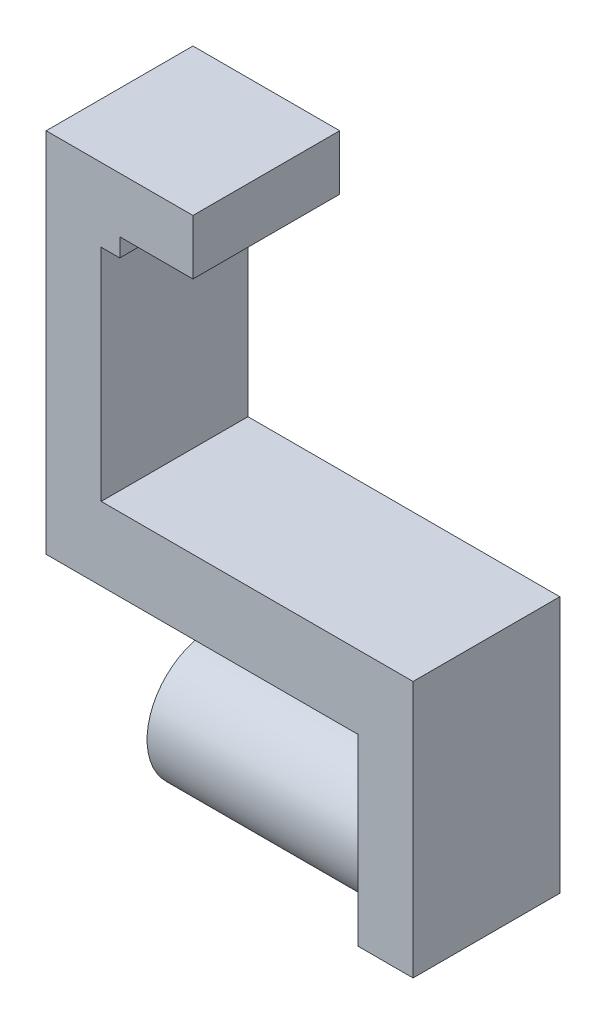
SolidWorks part; units mm, degrees
material "ASTM A36 Steel"
ref_plane "Front Plane" through (0, 0, 0) normal (0, 0, 1) x (1, 0, 0)
ref_plane "Top Plane" through (0, 0, 0) normal (0, 1, 0) x (1, 0, 0)
ref_plane "Right Plane" through (0, 0, 0) normal (1, 0, 0) x (0, 0, -1)
sketch "Sketch1" plane through (0, 0, 0) normal (1, 0, 0) x (0, 0, -1)
  circle A0 centre (0, 0) radius 11.1125
  dimension "D1" = 22.225
extrude "Boss-Extrude1" add sketch "Sketch1" against normal blind 38.1
sketch "Sketch2" plane through (0, 0, 0) normal (0, 0, 1) x (1, 0, 0)
  line L1 (0, -11.1125) -> (9.525, -11.1125)
  line L2 (0, -11.1125) -> (0, 20.6375)
  line L3 (0, 20.6375) -> (9.525, 20.6375)
  line L4 (9.525, -11.1125) -> (9.525, 20.6375)
  dimension "D1" = 9.525
  dimension "D2" = 31.75
  dimension "D3" = 11.1125
extrude "Boss-Extrude2" add sketch "Sketch2" along normal blind 12.7 and the other way blind 12.7
sketch "Sketch3" plane through (0, 0, 0) normal (0, 0, 1) x (1, 0, 0)
  line L1 (-53.975, 20.6375) -> (9.525, 20.6375)
  line L2 (-53.975, 20.6375) -> (-53.975, 33.3375)
  line L3 (-53.975, 33.3375) -> (9.525, 33.3375)
  line L4 (9.525, 20.6375) -> (9.525, 33.3375)
  dimension "D1" = 63.5
  dimension "D2" = 12.7
  dimension "D3" = 20.6375
  dimension "D4" = 53.975
extrude "Boss-Extrude3" add sketch "Sketch3" along normal blind 12.7 and the other way blind 12.7
sketch "Sketch4" plane through (0, 0, 0) normal (0, 0, 1) x (1, 0, 0)
  line L1 (-53.975, 20.6375) -> (-44.45, 20.6375)
  line L2 (-53.975, 20.6375) -> (-53.975, 84.1375)
  line L3 (-53.975, 84.1375) -> (-44.45, 84.1375)
  line L4 (-44.45, 20.6375) -> (-44.45, 84.1375)
  dimension "D1" = 9.525
  dimension "D3" = 20.6375
  dimension "D4" = 53.975
  dimension "D2" = 63.5
extrude "Boss-Extrude4" add sketch "Sketch4" along normal blind 12.7 and the other way blind 12.7
sketch "Sketch5" plane through (0, 0, 0) normal (0, 0, 1) x (1, 0, 0)
  line L5 (-53.975, 71.4375) -> (-41.2394, 71.4375)
  line L6 (-53.975, 84.1375) -> (-53.975, 20.6375) construction
  line L7 (-41.2394, 71.4375) -> (-41.2394, 74.6125)
  line L8 (-41.2394, 74.6125) -> (-28.575, 74.6125)
  line L9 (-28.575, 74.6125) -> (-28.575, 84.1375)
  line L10 (-28.575, 84.1375) -> (-53.975, 84.1375)
  line L11 (-53.975, 84.1375) -> (-53.975, 71.4375)
  dimension "D1" = 12.7
  dimension "D2" = 3.175
  dimension "D3" = 12.6644
  dimension "D4" = 25.4
  dimension "D5" = 84.1375
  dimension "D6" = 53.975
extrude "Boss-Extrude5" add sketch "Sketch5" along normal blind 12.7 and the other way blind 12.7
equation "\"F\" = 700"
equation "\"SF\" = 4"
equation "\"Sy\" = 36000"
equation "\"E\" = 29000000"
equation "\"dmax\" = 0.005"
equation "\"LA\" = 1.5"
equation "\"LB\" = 1.25"
equation "\"LC\" = 2.5"
equation "\"LD\" = 1.5"
equation "\"LE\" = 1"
equation "\"W\" = 1"
equation "\"tprac\" = 0.375"
equation "\"step\" = 0.125"
equation "\"slotW\" = 0.4986"
equation "\"slotD\" = 0.125"
equation "\"P\" = \"F\" / 2"
equation "\"sigA\" = \"Sy\" / \"SF\""
equation "\"MA\" = \"P\" * \"LA\""
equation "\"dAmin\" = ( 32 * \"MA\" / ( pi * \"sigA\" ) ) ^ ( 1 / 3 )"
equation "\"dA\" = ( int( \"dAmin\" / \"step\" ) + 1 ) * \"step\""
equation "\"MC\" = \"P\" * \"LC\" / 4"
equation "\"hCmin\" = sqr( 6 * \"MC\" / ( \"W\" * \"sigA\" ) )"
equation "\"hC\" = ( int( \"hCmin\" / \"step\" ) + 1 ) * \"step\""
equation "\"ME\" = ( \"P\" / 2 ) * \"LE\""
equation "\"hEmin\" = sqr( 6 * \"ME\" / ( \"W\" * \"sigA\" ) )"
equation "\"hE\" = ( int( ( \"hEmin\" + \"slotD\" ) / \"step\" ) + 1 ) * \"step\""
equation "\"tB\" = \"tprac\""
equation "\"tD\" = \"tprac\""
equation "\"yb\" = \"LB\" - \"dA\" / 2"
equation "\"hD\" = \"hC\" + \"LD\" + \"hE\""
equation "\"yD\" = \"yb\" + \"hD\""
equation "\"xl\" = \"LC\" - \"tB\""
equation "\"D1@Sketch1\" = \"dA\""
equation "\"D1@Sketch2\" = \"tB\""
equation "\"D2@Sketch2\" = \"LB\""
equation "\"D3@Sketch2\" = \"dA\" / 2"
equation "\"D1@Sketch3\" = \"LC\""
equation "\"D2@Sketch3\" = \"hC\""
equation "\"D3@Sketch3\" = \"yb\""
equation "\"D4@Sketch3\" = \"xl\""
equation "\"D1@Sketch4\" = \"tD\""
equation "\"D2@Sketch4\" = \"hD\""
equation "\"D1@Sketch5\" = \"hE\""
equation "\"D2@Sketch5\" = \"slotD\""
equation "\"D3@Sketch5\" = \"slotW\""
equation "\"D4@Sketch5\" = \"LE\""
equation "\"D5@Sketch5\"= \"yD\""
